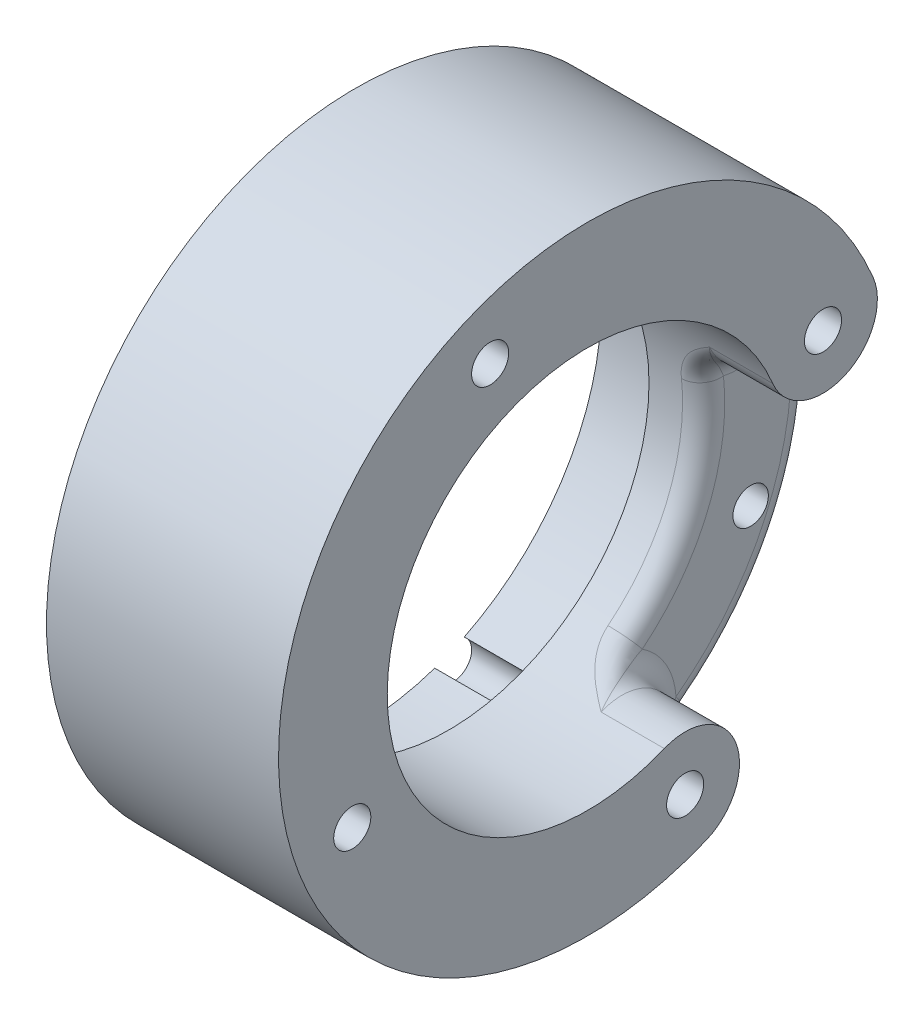
SolidWorks part; units mm, degrees
ref_plane "Front Plane" through (0, 0, 0) normal (0, 0, 1) x (1, 0, 0)
ref_plane "Top Plane" through (0, 0, 0) normal (0, 1, 0) x (1, 0, 0)
ref_plane "Right Plane" through (0, 0, 0) normal (1, 0, 0) x (0, 0, -1)
ref_axis "Axis1" through (-18.3356, 0, 0) along (1, 0, 0)
sketch "Sketch1" plane through (0, 0, 0) normal (1, 0, 0) x (0, 0, -1)
  line L0 (-13.9333, -5.7713) -> (-21.4917, -8.9022) construction
  circle A0 centre (0, 0) radius 15.0812
  circle A1 centre (0, 0) radius 23.2625
  arc A3 (-23.2625, 0) -> (16.8052, 16.085) centre (0, 0) ccw construction
  circle A4 centre (7.3368, -17.7125) radius 1.651 construction
  circle A5 centre (17.7125, 7.3368) radius 1.651 construction
  circle A6 centre (-7.3368, 17.7125) radius 1.651 construction
  circle A7 centre (-17.7125, -7.3368) radius 1.651 construction
  circle A8 centre (7.3368, -17.7125) radius 1.651 construction
  circle A9 centre (17.7125, 7.3368) radius 1.651 construction
  circle A10 centre (-7.3368, 17.7125) radius 1.651 construction
  circle A11 centre (-17.7125, -7.3368) radius 1.651 construction
  circle A12 centre (7.3368, -17.7125) radius 1.397
  circle A13 centre (17.7125, 7.3368) radius 1.397
  circle A14 centre (-7.3368, 17.7125) radius 1.397
  circle A15 centre (-17.7125, -7.3368) radius 1.397
  point P21 (-17.7125, -7.3368)
  dimension "D1" = 2.794
extrude "Boss-Extrude1" add sketch "Sketch1" against normal up to surface (17.4625 mm away)
sketch "Sketch2" plane through (-17.4625, 0, 0) normal (-1, 0, 0) x (0, 0, 1)
  circle A0 centre (0, 0) radius 18.5 construction
  circle A1 centre (0, 0) radius 18.5
extrude "Cut-Extrude1" cut sketch "Sketch2" against normal up to surface (7 mm away)
ref_plane "Plane1" through (0, 13.8153, -5.7225) normal (0, -0.9239, 0.3827) x (-1, 0, 0)
ref_plane "Plane2" through (0, -13.8153, 5.7225) normal (0, 0.9239, -0.3827) x (1, 0, 0)
ref_plane "Plane3" through (0, 0, 0) normal (0, 0.9239, -0.3827) x (1, 0, 0)
sketch "Sketch5" plane through (-17.4625, 0, 0) normal (-1, 0, 0) x (0, 0, 1)
  line L0 (16.2406, 6.7271) -> (-16.2406, -6.7271) construction
  circle A1 centre (18.6171, 7.7115) radius 1.651 construction
  circle A3 centre (18.6171, 7.7115) radius 1.3335
  arc A5 (17.5158, -5.9537) -> (8.1757, 16.5954) centre (0, 0) ccw construction
  circle A6 centre (0, 0) radius 20.151 construction
  dimension "D1" = 3.302
  dimension "D2" = 2.667
extrude "Cut-Extrude2" cut sketch "Sketch5" against normal blind 15.875
pattern_circular "CirPattern3" count 4 over 360 about axis through (-18.3356, 0, 0) along (1, 0, 0) of "Cut-Extrude2"
sketch "Sketch6" plane through (-17.4625, 0, 0) normal (-1, 0, 0) x (0, 0, 1)
  line L0 (-17.7125, 7.3368) -> (-13.9333, 5.7713) construction
  line L1 (-5.7713, -13.9333) -> (-7.3368, -17.7125) construction
  circle A0 centre (0, 0) radius 23.2625 construction
  circle A1 centre (0, 0) radius 15.0812 construction
  circle A2 centre (0, 0) radius 23.2625 construction
  circle A3 centre (0, 0) radius 15.0812 construction
  arc A4 (-13.9333, 5.7713) -> (-21.4917, 8.9022) centre (-17.7125, 7.3368) cw
  arc A5 (-5.7713, -13.9333) -> (-8.9022, -21.4917) centre (-7.3368, -17.7125) ccw
  arc A6 (-13.9333, 5.7713) -> (-5.7713, -13.9333) centre (0, 0) cw
  arc A7 (-21.4917, 8.9022) -> (-8.9022, -21.4917) centre (0, 0) cw
extrude "Cut-Extrude3" cut sketch "Sketch6" along normal blind 6.35 and the other way through all from surface flip side to cut starting at face at (0, -7.3368, 16.3155)
fillet "Fillet4" radius 1.5875 4 edges at (-6.35, 3.5575, -19.2779) (-6.35, -16.1471, -11.116) (-6.35, -8.9022, -21.4917) (-6.35, -5.7713, -13.9333)
